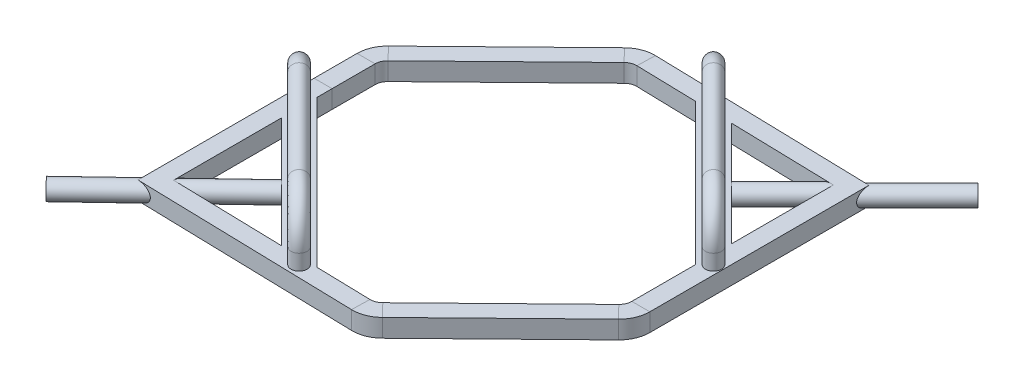
SolidWorks part; units mm, degrees
ref_plane "Front Plane" through (0, 0, 0) normal (0, 0, 1) x (1, 0, 0)
ref_plane "Top Plane" through (0, 0, 0) normal (0, 1, 0) x (1, 0, 0)
ref_plane "Right Plane" through (0, 0, 0) normal (1, 0, 0) x (0, 0, -1)
sketch "Sketch1" plane through (0, 0, 0) normal (0, 1, 0) x (1, 0, 0)
  line L0 (-214.4575, 257.5425) -> (785.5425, 257.5425) construction
  line L1 (-178.4769, 198.0197) -> (-279.7415, 99.2846) construction
  line L2 (30.248, 29.4924) -> (-30.248, -29.4924) construction
  line L3 (294.7069, -84.693) -> (92.1778, -282.163) construction
  line L4 (-178.4769, 198.0197) -> (193.4424, -183.428) construction
  line L5 (-290.8707, 72.8897) -> (-290.8707, -283.6049)
  line L6 (-279.7415, 99.2846) -> (-77.2124, 296.7547)
  line L7 (-50.5444, 307.2127) -> (305.8361, 298.1965)
  line L8 (305.8361, -58.2981) -> (305.8361, 298.1965)
  line L9 (92.1778, -282.163) -> (294.7069, -84.693)
  line L10 (65.5099, -292.6211) -> (-290.8707, -283.6049)
  arc A0 (-279.7415, 99.2846) -> (-290.8707, 72.8897) centre (-254.0059, 72.8897) ccw
  arc A1 (-77.2124, 296.7547) -> (-50.5444, 307.2127) centre (-51.4768, 270.3598) cw
  arc A2 (294.7069, -84.693) -> (305.8361, -58.2981) centre (268.9714, -58.2981) ccw
  arc A3 (92.1778, -282.163) -> (65.5099, -292.6211) centre (66.4423, -255.7681) cw
  point P6 (-178.4769, 198.0197)
sketch "Sketch3" plane through (0, 0, 0) normal (0, 0, 1) x (1, 0, 0)
  line L2 (-306.1489, 15.2782) -> (-275.5924, 15.2782)
  line L3 (-306.1489, 15.2782) -> (-306.1489, -15.2782)
  line L4 (-306.1489, -15.2782) -> (-275.5924, -15.2782)
  line L5 (-275.5924, 15.2782) -> (-275.5924, -15.2782)
sweep "Sweep1" add profiles "Sketch3" path "Sketch1"
sketch "Sketch4" plane through (0, 0, 0) normal (0, 1, 0) x (1, 0, 0)
  line L0 (66.4423, 304.253) -> (305.8361, 64.8592) construction
  line L1 (-178.4769, 198.0197) -> (193.4424, -183.428) construction
  line L2 (-290.8707, -44.1344) -> (-57.608, -289.5063) construction
  line L6 (-290.8707, -283.6049) -> (65.5099, -292.6211)
  line L7 (-290.8707, 72.8897) -> (-290.8707, -283.6049)
  line L8 (-77.2124, 296.7547) -> (-279.7415, 99.2846)
  line L9 (305.8361, 298.1965) -> (-50.5444, 307.2127)
  line L10 (305.8361, -58.2981) -> (305.8361, 298.1965)
  line L11 (92.1778, -282.163) -> (294.7069, -84.693)
  line L12 (-290.8707, -283.6049) -> (65.5099, -292.6211)
  line L13 (-290.8707, 72.8897) -> (-290.8707, -283.6049)
  line L14 (-77.2124, 296.7547) -> (-279.7415, 99.2846)
  line L15 (305.8361, 298.1965) -> (-50.5444, 307.2127)
  line L16 (305.8361, -58.2981) -> (305.8361, 298.1965)
  line L17 (92.1778, -282.163) -> (294.7069, -84.693)
  arc A4 (-279.7415, 99.2846) -> (-290.8707, 72.8897) centre (-254.0059, 72.8897) ccw
  arc A5 (-50.5444, 307.2127) -> (-77.2124, 296.7547) centre (-51.4768, 270.3598) ccw
  arc A6 (294.7069, -84.693) -> (305.8361, -58.2981) centre (268.9714, -58.2981) ccw
  arc A7 (65.5099, -292.6211) -> (92.1778, -282.163) centre (66.4423, -255.7681) ccw
  arc A8 (-279.7415, 99.2846) -> (-290.8707, 72.8897) centre (-254.0059, 72.8897) ccw
  arc A9 (-50.5444, 307.2127) -> (-77.2124, 296.7547) centre (-51.4768, 270.3598) ccw
  arc A10 (294.7069, -84.693) -> (305.8361, -58.2981) centre (268.9714, -58.2981) ccw
  arc A11 (65.5099, -292.6211) -> (92.1778, -282.163) centre (66.4423, -255.7681) ccw
  dimension "D1" = 0
ref_plane "Plane2" through (185.3477, 0, -185.3477) normal (-0.7071, 0, 0.7071) x (0.7071, 0, 0.7071)
sketch "Sketch5" plane through (185.3477, 0, -185.3477) normal (-0.7071, 0, 0.7071) x (0.7071, 0, 0.7071)
  line L2 (170.3964, 0) -> (170.3964, 41.5267)
  line L3 (111.9764, 99.9467) -> (-109.7376, 99.9467)
  line L4 (-168.1576, 0) -> (-168.1576, 41.5267)
  arc A0 (170.3964, 41.5267) -> (111.9764, 99.9467) centre (111.9764, 41.5267) ccw
  arc A1 (-109.7376, 99.9467) -> (-168.1576, 41.5267) centre (-109.7376, 41.5267) ccw
  dimension "D1" = 58.42
  dimension "D2" = 41.5267
sketch "Sketch6" plane through (0, 0, 0) normal (0, 1, 0) x (1, 0, 0)
  circle A0 centre (66.4423, 304.253) radius 13.601
sweep "Sweep2" add profiles "Sketch6" path "Sketch5"
sketch "Sketch7" plane through (185.3477, 0, -185.3477) normal (-0.7071, 0, 0.7071) x (0.7071, 0, 0.7071)
  line L0 (-168.1576, 0) -> (170.3964, 0)
ref_plane "Plane3" through (-119.6969, 0, -122.7635) normal (0.6981, 0, 0.716) x (0.716, 0, -0.6981)
sketch "Sketch8" plane through (-119.6969, 0, -122.7635) normal (0.6981, 0, 0.716) x (0.716, 0, -0.6981)
  line L0 (189.2172, 15.2782) -> (448.4883, 15.2782) construction
  line L1 (238.635, -15.2782) -> (281.3121, -15.2782)
  line L2 (238.635, -15.2782) -> (238.635, 15.2782)
  line L3 (238.635, 15.2782) -> (281.3121, 15.2782)
  line L4 (281.3121, -15.2782) -> (281.3121, 15.2782)
  line L5 (238.635, -15.2782) -> (281.3121, 15.2782) construction
  line L6 (238.635, 15.2782) -> (281.3121, -15.2782) construction
  point P0 (259.9736, 0)
sweep "Sweep3" add profiles "Sketch8" path "Sketch7"
sketch "Sketch9" plane through (200.4351, 0, -200.4351) normal (0.7071, 0, -0.7071) x (-0.7071, 0, -0.7071)
  line L0 (263.4992, 15.2782) -> (-5.6719, 15.2782) construction
  line L1 (263.4992, -15.2782) -> (-5.6719, -15.2782) construction
  circle A0 centre (-2.5285, 0) radius 15.2782
extrude "Boss-Extrude1" add sketch "Sketch9" along normal blind 131.572
ref_plane "Plane4" through (294.9068, 0, -294.9068) normal (-0.7071, 0, 0.7071) x (0.7071, 0, 0.7071)
sketch "Sketch10" plane through (294.9068, 0, -294.9068) normal (-0.7071, 0, 0.7071) x (0.7071, 0, 0.7071)
  line L0 (257.4818, 0) -> (5.402, 0) construction
  circle A0 centre (5.402, 0) radius 15.0865
extrude "Boss-Extrude2" add sketch "Sketch10" against normal blind 162.052
ref_plane "Plane5" through (9.7714, 0, -9.7714) normal (-0.7071, 0, 0.7071) x (0.7071, 0, 0.7071)
ref_plane "Plane6" through (-174.8285, 0, 166.2006) normal (-0.7248, 0, 0.689) x (0.689, 0, 0.7248)
sketch "Sketch11" plane through (-174.8285, 0, 166.2006) normal (-0.7248, 0, 0.689) x (0.689, 0, 0.7248)
  line L0 (252.9725, 0) -> (-5.402, 0) construction
  line L1 (5.4075, 15.2782) -> (-210.9356, 15.2782) construction
  line L2 (268.0208, -15.2782) -> (5.4075, -15.2782) construction
  circle A0 centre (5.3829, 0) radius 15.2782
extrude "Boss-Extrude3" add sketch "Sketch11" along normal blind 296.164
mirror "Mirror1" about plane through (9.7714, 0, -9.7714) normal (-0.7071, 0, 0.7071) of "Sweep2", "Sweep3"
sketch "Sketch12" plane through (-122.5132, 0, -119.4529) normal (-0.716, 0, -0.6981) x (-0.6981, 0, 0.716)
  line L6 (219.2773, -15.2782) -> (219.2773, 0)
  line L7 (219.2773, 0) -> (218.7372, 0)
  line L8 (218.7372, 0) -> (218.7372, 15.2782)
  line L9 (218.7372, 15.2782) -> (210.9997, 15.2782)
  line L10 (210.9997, 15.2782) -> (210.9997, -15.2782)
  line L11 (210.9997, -15.2782) -> (219.2773, -15.2782)
  line L12 (219.2773, -15.2782) -> (219.2773, 0)
  line L13 (219.2773, 0) -> (218.7372, 0)
  line L14 (218.7372, 0) -> (218.7372, 15.2782)
  line L15 (218.7372, 15.2782) -> (210.9997, 15.2782)
  line L16 (210.9997, 15.2782) -> (210.9997, -15.2782)
  line L17 (210.9997, -15.2782) -> (219.2773, -15.2782)
  dimension "D1" = 0
extrude "Boss-Extrude4" add sketch "Sketch12" along normal up to next
sketch "Sketch13" plane through (119.8696, 0, 116.8754) normal (0.716, 0, 0.6981) x (0.6981, 0, -0.716)
  line L4 (-215.2812, 15.2782) -> (-220.5914, 15.2782)
  line L5 (-220.5914, 15.2782) -> (-220.5914, -15.2782)
  line L6 (-220.5914, -15.2782) -> (-215.2812, -15.2782)
  line L7 (-215.2812, -15.2782) -> (-215.2812, 15.2782)
  line L8 (-215.2812, 15.2782) -> (-220.5914, 15.2782)
  line L9 (-220.5914, 15.2782) -> (-220.5914, -15.2782)
  line L10 (-220.5914, -15.2782) -> (-215.2812, -15.2782)
  line L11 (-215.2812, -15.2782) -> (-215.2812, 15.2782)
  dimension "D1" = 0
extrude "Boss-Extrude5" add sketch "Sketch13" along normal up to next
scale "Scale1" scale about centroid uniform scaling yes scale factor 1.5
